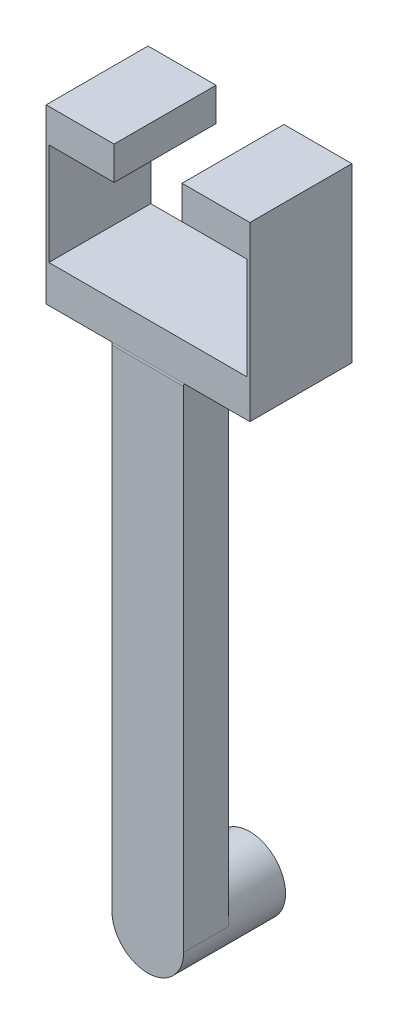
SolidWorks part; units mm, degrees
material "6061-T6 (SS)"
ref_plane "Front Plane" through (0, 0, 0) normal (0, 0, 1) x (1, 0, 0)
ref_plane "Top Plane" through (0, 0, 0) normal (0, 1, 0) x (1, 0, 0)
ref_plane "Right Plane" through (0, 0, 0) normal (1, 0, 0) x (0, 0, -1)
sketch "Sketch2" plane through (0, 0, 0) normal (0, 0, 1) x (1, 0, 0)
  circle A0 centre (0, 0) radius 13.4112
  dimension "D1" = 26.8224
extrude "Boss-Extrude1" add sketch "Sketch2" along normal blind 38.1
sketch "Sketch5" plane through (0, 0, 38.1) normal (0, 0, 1) x (1, 0, 0)
  line L1 (-13.4112, 0) -> (13.4112, 0)
  line L2 (-13.4112, 0) -> (-13.4112, 184.15)
  line L3 (-13.4112, 184.15) -> (13.4112, 184.15)
  line L4 (13.4112, 0) -> (13.4112, 184.15)
  circle A0 centre (0, 0) radius 13.4112 construction
  dimension "D1" = 26.8224
  dimension "D2" = 184.15
extrude "Boss-Extrude2" add sketch "Sketch5" against normal blind 16.7386
sketch "Sketch8" plane through (0, 184.15, 0) normal (0, 1, 0) x (1, 0, 0)
  line L1 (-38.1, 0.1018) -> (38.1, 0.1018)
  line L3 (-38.1, 0.1018) -> (-38.1, -37.9982)
  line L4 (-38.1, -37.9982) -> (38.1, -37.9982)
  line L5 (38.1, 0.1018) -> (38.1, -37.9982)
  dimension "D1" = 38.1
  dimension "D2" = 76.2
extrude "Boss-Extrude3" add sketch "Sketch8" along normal blind 13.97
sketch "Sketch9" plane through (0, 198.12, 0) normal (0, 1, 0) x (1, 0, 0)
  line L0 (-38.1, -37.9982) -> (38.1, -37.9982) construction
  line L1 (-38.1, 0.1018) -> (-37.084, 0.1018)
  line L2 (-38.1, 0.1018) -> (-38.1, -37.9982)
  line L3 (-38.1, -37.9982) -> (-37.084, -37.9982)
  line L4 (-37.084, 0.1018) -> (-37.084, -37.9982)
  line L6 (38.1, 0.1018) -> (37.084, 0.1018)
  line L7 (38.1, 0.1018) -> (38.1, -37.9982)
  line L8 (38.1, -37.9982) -> (37.084, -37.9982)
  line L9 (37.084, 0.1018) -> (37.084, -37.9982)
  dimension "D1" = 1.016
  dimension "D2" = 1.016
extrude "Boss-Extrude4" add sketch "Sketch9" along normal blind 38.1
sketch "Sketch10" plane through (0, 236.22, 0) normal (0, 1, 0) x (1, 0, 0)
  line L0 (-37.084, -37.9982) -> (37.084, -37.9982) construction
  line L1 (-38.1, 0.1018) -> (-12.7, 0.1018)
  line L2 (-38.1, 0.1018) -> (-38.1, -37.9982)
  line L3 (-38.1, -37.9982) -> (-12.7, -37.9982)
  line L4 (-12.7, 0.1018) -> (-12.7, -37.9982)
  line L6 (38.1, 0.1018) -> (12.7, 0.1018)
  line L7 (38.1, 0.1018) -> (38.1, -37.9982)
  line L8 (38.1, -37.9982) -> (12.7, -37.9982)
  line L9 (12.7, 0.1018) -> (12.7, -37.9982)
  dimension "D1" = 25.4
  dimension "D2" = 25.4
extrude "Boss-Extrude5" add sketch "Sketch10" along normal blind 12.446
fillet "Fillet1" radius 3.81 1 edges at (0, 184.15, 38.1)
equation "\"F\"= 600"
equation "\"Sy\"= 40000"
equation "\"E\"= 10000000"
equation "\"Defmax\"= 0.005in"
equation "\"a\"= 0.498in"
equation "\"b\"= 0.9992in"
equation "\"c\"= 1.499in"
equation "\"d\"= 2.4964in"
equation "\"rA\"= 0.528in"
equation "\"aB\"= 0.696in"
equation "\"tB\"= ( ( 1200 * 7.25 * 4 ) / ( \"E\" * \"Defmax\" ) ) / 1.15"
equation "\"hC\"= 0.5473in"
equation "\"LC\"= 2.4964in"
equation "\"WC\"= 1.5in"
equation "\"aD\"= 0.06in"
equation "\"DL\"= ( ( 600 / 1000 ) / \"WD\" )"
equation "\"WD\"= 1.499in"
equation "\"eH\"= 0.4897in"
equation "\"LE\"= 0.9992in"
equation "\"WE\"= 1.50in"
equation "\"D1@Sketch2\"= \"rA\" * 2"
equation "\"LA\"= 1.5in"
